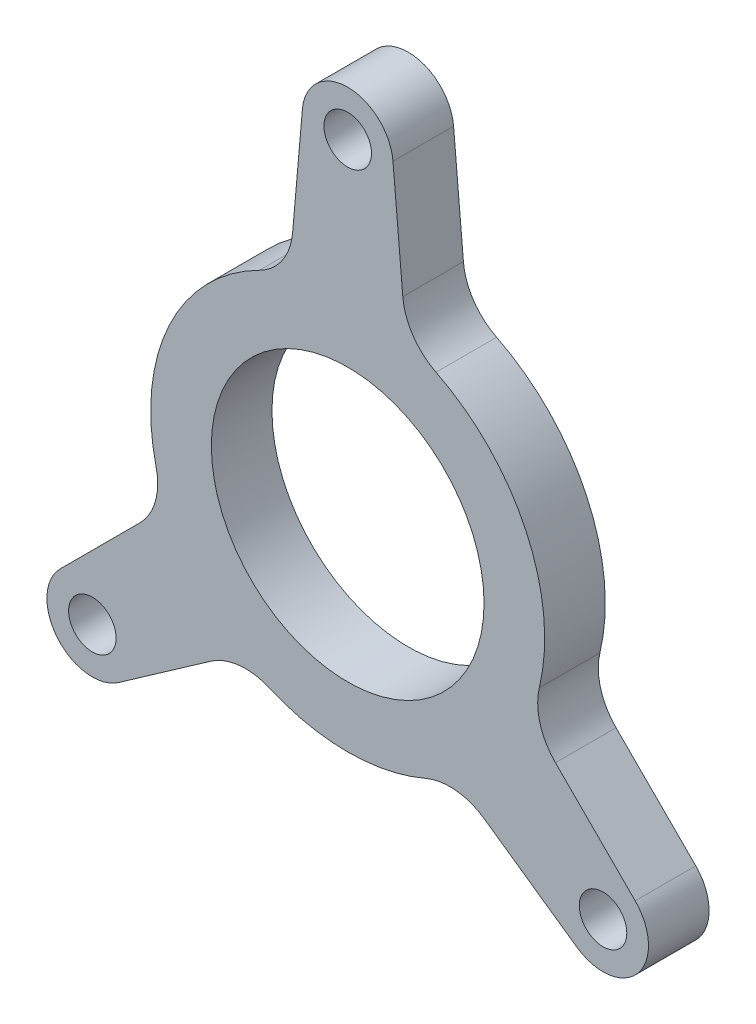
SolidWorks part; units mm, degrees
material "6061-T6 (SS)"
ref_plane "Front Plane" through (0, 0, 0) normal (0, 0, 1) x (1, 0, 0)
ref_plane "Top Plane" through (0, 0, 0) normal (0, 1, 0) x (1, 0, 0)
ref_plane "Right Plane" through (0, 0, 0) normal (1, 0, 0) x (0, 0, -1)
sketch "Sketch1" plane through (0, 0, 0) normal (0, 0, 1) x (1, 0, 0)
  line L0 (0, 0) -> (0, 34.925) construction
  line L1 (0, 0) -> (26.7541, -22.4494) construction
  line L2 (0, 0) -> (-26.7541, -22.4494) construction
  line L3 (-4.7444, 35.3401) -> (-6.1117, 19.7118)
  line L4 (4.7444, 35.3401) -> (6.1117, 19.7118)
  line L5 (30.1217, -19.0818) -> (19.0286, -7.9887)
  line L6 (24.0224, -26.3506) -> (11.1716, -17.3523)
  line L7 (-24.0224, -26.3506) -> (-11.1716, -17.3523)
  line L8 (-19.0286, -7.9887) -> (-30.1217, -19.0818)
  circle A0 centre (26.7541, -22.4494) radius 4.7625
  circle A1 centre (0, 34.925) radius 4.7625
  circle A2 centre (-26.7541, -22.4494) radius 4.7625
  circle A3 centre (26.7541, -22.4494) radius 2.4892
  circle A4 centre (-26.7541, -22.4494) radius 2.4892
  circle A5 centre (0, 34.925) radius 2.4892
  circle A6 centre (0, 0) radius 14.2875
  circle A7 centre (0, 0) radius 20.6375
  dimension "D1" = 9.525
  dimension "D4" = 4.9784
  dimension "D13" = 6.35
  dimension "D14" = 28.575
  dimension "D2" = 34.925
  dimension "D5" = 130
  dimension "D6" = 130
  dimension "D7" = 5
  dimension "D8" = 5
  dimension "D9" = 5
  dimension "D10" = 5
  dimension "D11" = 5
  dimension "D12" = 5
extrude "Boss-Extrude1" add sketch "Sketch1" along normal mid plane 6.35 contours A7 A6 | A7 L4 A1 L3 | A7 L6 A0 L5 | A7 L8 A2 L7 | A2 A4 | A1 A5 | A0 A3 region at (0, 25.7229, 0) region at (0, 39.5528, 0) region at (0, 20.0538, 0) region at (-19.7049, -16.5343, 0) region at (-24.9831, -18.1738, 0) region at (19.7049, -16.5343, 0) region at (31.0296, -20.6784, 0)
fillet "Fillet1" radius 6.35 6 edges at (19.0286, -7.9887, 0) (11.1716, -17.3523, 0) (-11.1716, -17.3523, 0) (-19.0286, -7.9887, 0) (-6.1117, 19.7118, 0) (6.1117, 19.7118, 0)
